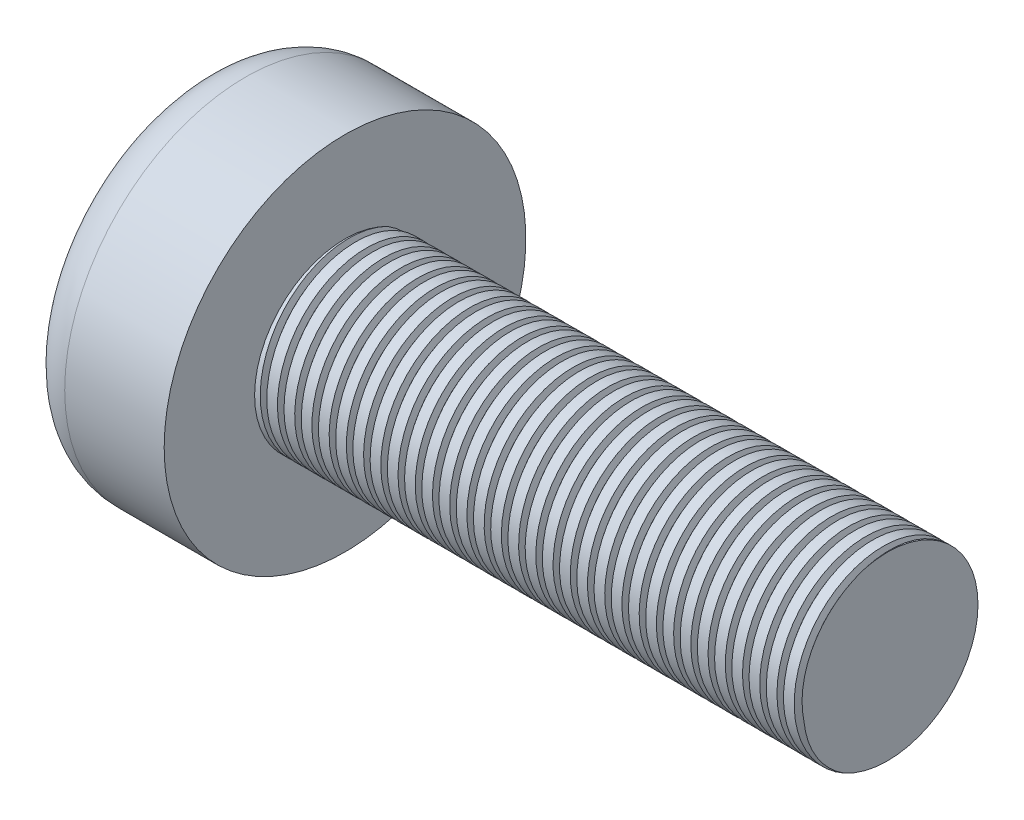
SolidWorks part; units mm, degrees
ref_plane "Plan de face" through (0, 0, 0) normal (0, 0, 1) x (1, 0, 0)
ref_plane "Plan de dessus" through (0, 0, 0) normal (0, 1, 0) x (1, 0, 0)
ref_plane "Plan de droite" through (0, 0, 0) normal (1, 0, 0) x (0, 0, -1)
sketch "Esquisse1" plane through (0, 0, 0) normal (0, 0, 1) x (1, 0, 0)
  line L0 (1.92, 2.4) -> (0.6, 2.4)
  line L1 (0, 0) -> (1.92, 0)
  line L2 (1.92, 0) -> (9.12, 0)
  line L3 (9.12, 0) -> (9.12, 1.2)
  line L4 (9.12, 1.2) -> (1.92, 1.2)
  line L5 (1.92, 1.2) -> (1.92, 2.4)
  line L6 (0, 1.8) -> (0, 0)
  arc A0 (0, 1.8) -> (0.6, 2.4) centre (0.6, 1.8) cw
  dimension "D5" = 0.6
  dimension "D1" = 1.92
  dimension "D2" = 7.2
  dimension "D3" = 1.2
  dimension "D4" = 1.2
revolve "Révolution1" add sketch "Esquisse1" angle 360 about L2
sketch "Esquisse2" plane through (9.12, 0, 0) normal (1, 0, 0) x (0, 0, -1)
  circle A0 centre (0, 0) radius 1.2
curve "Hélice/Spirale1" pitch 0.2286 height 7.2 turns 31.5
ref_plane "Plan1" through (9.12, 0, 1.2) normal (-0.0303, 0.9995, 0) x (0.9995, 0.0303, 0)
sketch "Esquisse9" plane through (9.12, 0, 1.2) normal (-0.0303, 0.9995, 0) x (0.9995, 0.0303, 0)
  line L4 (0.0651, -0.0234) -> (-0.0059, 0.0742)
  line L5 (-0.0059, 0.0742) -> (-0.0549, -0.0361)
  line L6 (-0.0549, -0.0361) -> (0.0651, -0.0234)
  circle A0 centre (0.0014, 0.0049) radius 0.0348 construction
  dimension "D1" = 0.12
sweep "Enlèvement de matière-Balayage2" cut profiles "Esquisse9" path "Hélice/Spirale1" align with end faces yes
sketch "Esquisse10" plane through (0, 0, 0) normal (1, 0, 0) x (0, 0, -1)
  line L0 (0, 0) -> (0, 1.404) construction
  line L1 (0.378, 1.404) -> (-0.378, 1.404)
  line L2 (0.378, 1.404) -> (0.378, 0.378)
  line L3 (0.378, -1.404) -> (-0.378, -1.404)
  line L4 (0.378, -1.404) -> (0.378, -0.3783)
  line L5 (-0.378, -1.404) -> (-0.378, -0.3783)
  line L6 (0.378, 0.378) -> (1.404, 0.378)
  line L7 (1.404, 0.378) -> (1.404, -0.378)
  line L8 (1.404, -0.378) -> (0.378, -0.3783)
  line L9 (-0.378, 1.404) -> (-0.378, 0.378)
  line L10 (-1.404, 0.378) -> (-1.404, -0.378)
  line L11 (-0.378, 0.378) -> (-1.404, 0.378)
  line L12 (-1.404, -0.378) -> (-0.378, -0.3783)
  point P6 (0, 1.404)
  point P18 (1.404, 0)
  dimension "D1" = 1.404
  dimension "D2" = 0.756
  dimension "D4" = 0.756
extrude "Enlèv. mat.-Extru.1" cut sketch "Esquisse10" along normal blind 0.6
